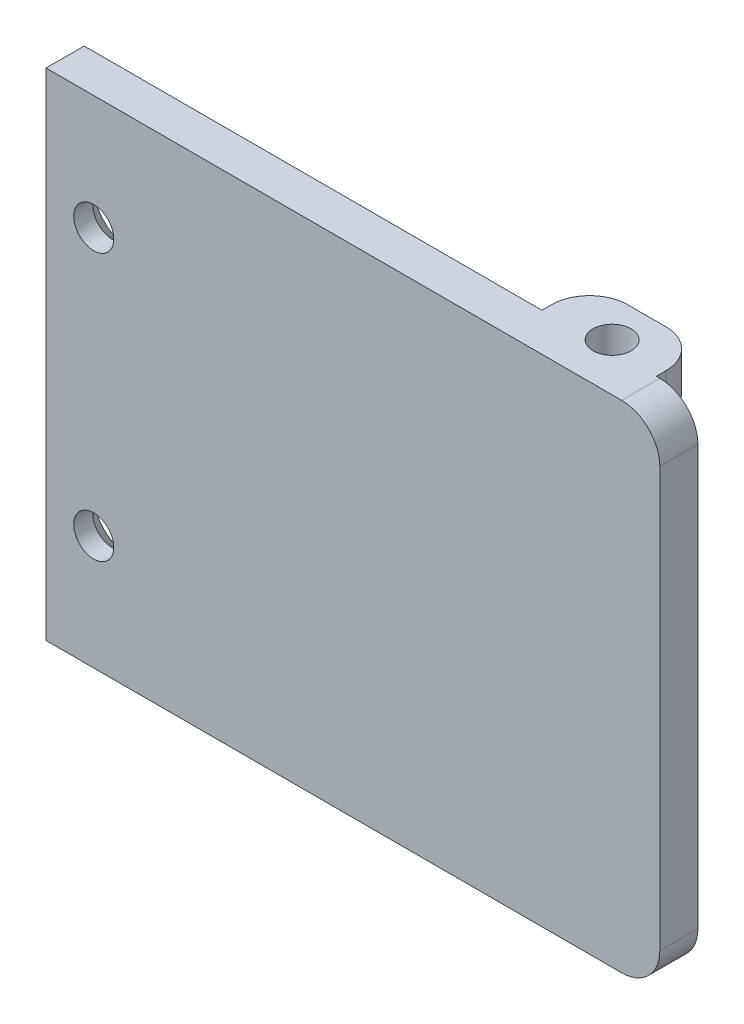
SolidWorks part; units mm, degrees
ref_plane "前视基准面" through (0, 0, 0) normal (0, 0, 1) x (1, 0, 0)
ref_plane "上视基准面" through (0, 0, 0) normal (0, 1, 0) x (1, 0, 0)
ref_plane "右视基准面" through (0, 0, 0) normal (1, 0, 0) x (0, 0, -1)
other "Configuration Table"
sketch "草图2" plane through (0, 0, 0) normal (0, 0, 1) x (1, 0, 0)
  line L1 (15.1907, -6.4342) -> (-16.9928, -6.4342)
  line L2 (15.1907, -6.4342) -> (15.1907, -32.4342)
  line L3 (15.1907, -32.4342) -> (-16.9928, -32.4342)
  line L4 (-16.9928, -6.4342) -> (-16.9928, -32.4342)
  line L6 (13.1907, -6.4342) -> (-12.8093, -6.4342) construction
  dimension "D1" = 32.1835
  dimension "D2" = 26
extrude "凸台-拉伸1" add sketch "草图2" along normal blind 2
fillet "圆角1" radius 2 2 edges at (15.1907, -32.4342, 1) (15.1907, -6.4342, 1)
sketch "草图4" plane through (0, 0, 0) normal (0, 0, -1) x (-1, 0, 0)
  line L0 (-13.1907, -6.4342) -> (16.9928, -6.4342) construction
  line L1 (16.9928, -6.4342) -> (16.9928, -32.4342) construction
  line L4 (16.9928, -32.4342) -> (-13.1907, -32.4342) construction
  circle A0 centre (14.4928, -12.4342) radius 1.05
  circle A1 centre (14.4928, -26.4342) radius 1.05
  dimension "D1" = 2.1
  dimension "D2" = 6
  dimension "D3" = 6
  dimension "D4" = 2.5
extrude "切除-拉伸2" cut sketch "草图4" against normal up to next
chamfer "倒角1" distance 1 angle 45 2 edges at (-15.5428, -12.4342, 0) (-15.5428, -26.4342, 0)
sketch "草图5" plane through (0, 0, 0) normal (0, 0, -1) x (-1, 0, 0)
  line L1 (-13.0072, -6.4342) -> (-7.0072, -6.4342)
  line L2 (-13.0072, -6.4342) -> (-13.0072, -8.4342)
  line L3 (-13.0072, -8.4342) -> (-7.0072, -8.4342)
  line L4 (-7.0072, -6.4342) -> (-7.0072, -8.4342)
  line L5 (16.9928, -32.4342) -> (-13.1907, -32.4342) construction
  line L6 (-13.0072, -32.4342) -> (-7.0072, -32.4342)
  line L7 (-13.0072, -32.4342) -> (-13.0072, -30.4342)
  line L8 (-13.0072, -30.4342) -> (-7.0072, -30.4342)
  line L9 (-7.0072, -32.4342) -> (-7.0072, -30.4342)
  line L11 (16.9928, -6.4342) -> (16.9928, -32.4342) construction
  line L12 (-13.1907, -6.4342) -> (16.9928, -6.4342) construction
  dimension "D1" = 2
  dimension "D2" = 24
  dimension "D3" = 6
extrude "凸台-拉伸2" add sketch "草图5" along normal blind 2.5
fillet "圆角2" radius 2 4 edges at (7.0072, -7.4342, -2.5) (13.0072, -7.4342, -2.5) (7.0072, -31.4342, -2.5) (13.0072, -31.4342, -2.5)
sketch "草图6" plane through (0, -32.4342, 0) normal (0, -1, 0) x (1, 0, 0)
  line L1 (17.1907, 2) -> (17.1907, -8) construction
  line L2 (-16.9928, 2) -> (13.1907, 2) construction
  circle A0 centre (10.1907, -0.5) radius 1
  point P2 (0, 0)
  dimension "D1" = 2
  dimension "D2" = 7
  dimension "D3" = 2.5
extrude "切除-拉伸3" cut sketch "草图6" against normal blind 4 draft 2
sketch "草图7" plane through (0, -6.4342, 0) normal (0, 1, 0) x (1, 0, 0)
  circle A0 centre (10.1907, 0.5) radius 1
  arc A1 (10.9751, 0) -> (9.4064, 0) centre (10.1907, 0.5) ccw construction
extrude "切除-拉伸4" cut sketch "草图7" against normal blind 4 draft 2
